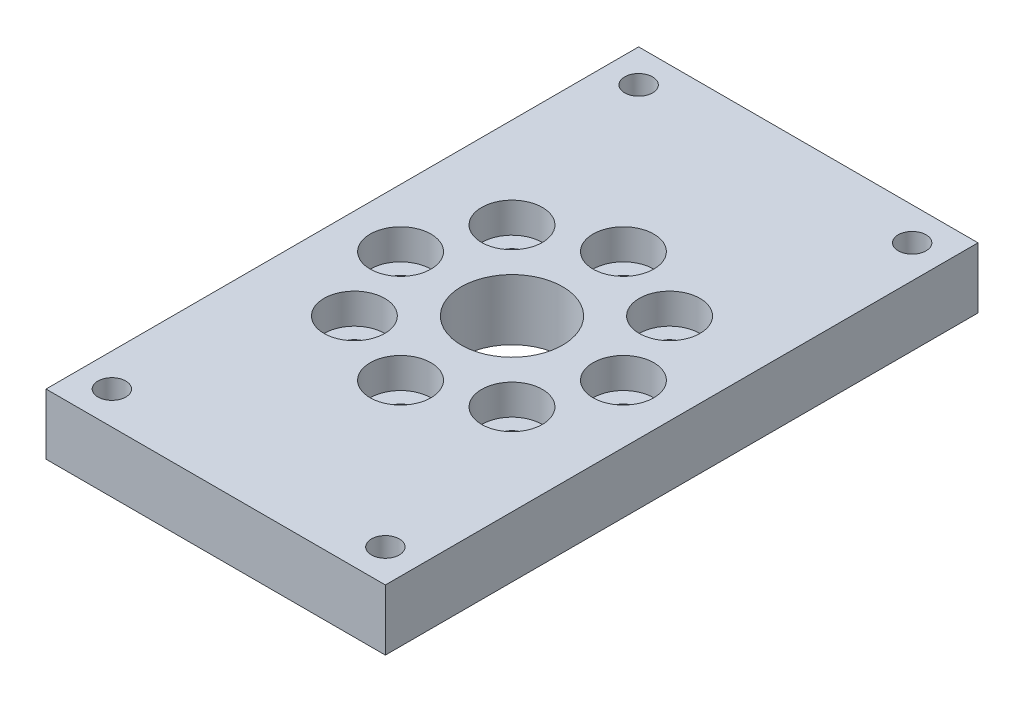
SolidWorks part; units mm, degrees
ref_plane "Front Plane" through (0, 0, 0) normal (0, 0, 1) x (1, 0, 0)
ref_plane "Top Plane" through (0, 0, 0) normal (0, 1, 0) x (1, 0, 0)
ref_plane "Right Plane" through (0, 0, 0) normal (1, 0, 0) x (0, 0, -1)
sketch "Sketch1" plane through (0, 0, 0) normal (0, 1, 0) x (1, 0, 0)
  line L1 (29.25, -16.75) -> (-29.25, -16.75)
  line L2 (29.25, -16.75) -> (29.25, 16.75)
  line L3 (29.25, 16.75) -> (-29.25, 16.75)
  line L4 (-29.25, -16.75) -> (-29.25, 16.75)
  line L5 (29.25, -16.75) -> (-29.25, 16.75) construction
  line L6 (29.25, 16.75) -> (-29.25, -16.75) construction
  circle A0 centre (-26, 13.5) radius 1.375
  circle A1 centre (-26, -13.5) radius 1.375
  circle A2 centre (26, 13.5) radius 1.375
  circle A3 centre (26, -13.5) radius 1.375
  point P0 (0, 0)
  dimension "D3" = 27
  dimension "D4" = 2.75
  dimension "D5" = 2.75
  dimension "D6" = 3.25
  dimension "D7" = 52
  dimension "D8" = 2.75
  dimension "D9" = 2.75
  dimension "D10" = 27
  dimension "D11" = 52
  dimension "D12" = 3.25
  dimension "D1" = 33.5
  dimension "D2" = 58.5
extrude "Boss-Extrude1" add sketch "Sketch1" along normal blind 6
sketch "Sketch2" plane through (0, 6, 0) normal (0, 1, 0) x (1, 0, 0)
  circle A0 centre (0, 0) radius 11
  circle A1 centre (-26, 13.5) radius 1.375 construction
  circle A2 centre (0, 11) radius 1.375
  circle A3 centre (7.7782, 7.7782) radius 1.375
  circle A4 centre (11, 0) radius 1.375
  circle A5 centre (7.7782, -7.7782) radius 1.375
  circle A6 centre (0, -11) radius 1.375
  circle A7 centre (-7.7782, -7.7782) radius 1.375
  circle A8 centre (-11, 0) radius 1.375
  circle A9 centre (-7.7782, 7.7782) radius 1.375
  point P22 (0, 0)
  dimension "D1" = 26
  dimension "D2" = 22
  dimension "D3" = 2.75
  dimension "D4" = 8
extrude "Cut-Extrude1" cut sketch "Sketch2" against normal blind 19 contours A9 | A2 | A3 | A4 | A5 | A6 | A7 | A8
sketch "Sketch3" plane through (0, 6, 0) normal (0, 1, 0) x (1, 0, 0)
  circle A0 centre (0, 0) radius 5
  dimension "D1" = 10
extrude "Cut-Extrude2" cut sketch "Sketch3" against normal blind 19
sketch "Sketch4" plane through (0, 6, 0) normal (0, 1, 0) x (1, 0, 0)
  circle A0 centre (-7.7782, 7.7782) radius 3
  circle A1 centre (0, 11) radius 3
  circle A2 centre (7.7782, 7.7782) radius 3
  circle A3 centre (11, 0) radius 3
  circle A4 centre (7.7782, -7.7782) radius 3
  circle A5 centre (0, -11) radius 3
  circle A6 centre (-7.7782, -7.7782) radius 3
  circle A7 centre (-11, 0) radius 3
  point P19 (0, 0)
  dimension "D1" = 6
  dimension "D2" = 8
extrude "Cut-Extrude3" cut sketch "Sketch4" against normal blind 3
sketch "Sketch5" plane through (0, 0, 0) normal (0, -1, 0) x (1, 0, 0)
  circle A0 centre (-26, 13.5) radius 3
  circle A1 centre (26, 13.5) radius 3
  circle A2 centre (26, -13.5) radius 3
  circle A3 centre (-26, -13.5) radius 3
  dimension "D1" = 6
  dimension "D2" = 6
  dimension "D3" = 6
  dimension "D4" = 6
extrude "Cut-Extrude4" cut sketch "Sketch5" against normal blind 3
move or copy body "Body-Move/Copy1" bodies to move or copy 105 copy no rotation origin (-1, 2, 1) rotation axis (-0.5774, -0.5774, 0.5774) rotation angle 120
move or copy body "Body-Move/Copy2" bodies to move or copy 106 copy no rotation origin (0, 3, 0) rotation axis (1, 0, 0) rotation angle 90
